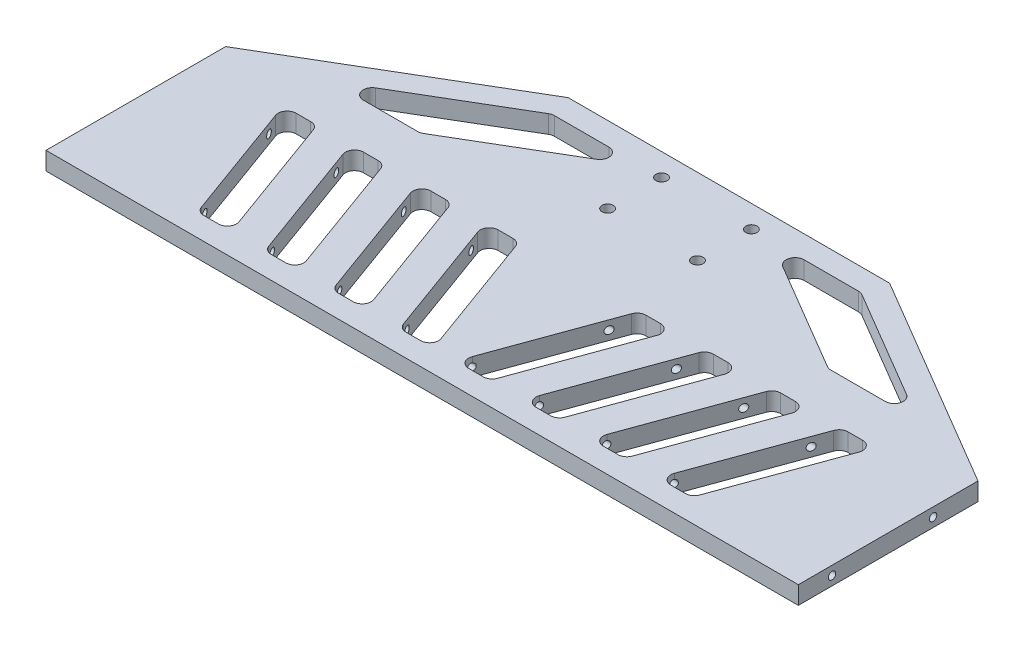
SolidWorks part; units mm, degrees
ref_plane "Ebene vorne" through (0, 0, 0) normal (0, 0, 1) x (1, 0, 0)
ref_plane "Ebene oben" through (0, 0, 0) normal (0, 1, 0) x (1, 0, 0)
ref_plane "Ebene rechts" through (0, 0, 0) normal (1, 0, 0) x (0, 0, -1)
sketch "Skizze3" plane through (0, 0, 0) normal (0, 1, 0) x (1, 0, 0)
  line L0 (0, 0) -> (0, 96.5783) construction
  line L1 (167.5, -40) -> (-167.5, -40)
  line L2 (167.5, -40) -> (167.5, 40)
  line L3 (-167.5, 40) -> (-71.5557, 96.5783)
  line L4 (-167.5, -40) -> (-167.5, 40)
  line L5 (167.5, -40) -> (-167.5, 40) construction
  line L6 (167.5, 40) -> (-167.5, -40) construction
  line L7 (-71.5557, 96.5783) -> (71.5557, 96.5783)
  line L8 (167.5, 40) -> (71.5557, 96.5783)
  circle A0 centre (-20, 86.5783) radius 2.5
  circle A1 centre (-20, 62.5783) radius 2.5
  circle A2 centre (20, 62.5783) radius 2.5
  circle A3 centre (20, 86.5783) radius 2.5
  point P0 (0, 0)
  dimension "D3" = 5
  dimension "D4" = 5
  dimension "D8" = 10
  dimension "D1" = 335
  dimension "D2" = 80
  dimension "D5" = 24
  dimension "D6" = 20
  dimension "D7" = 20
extrude "Aufsatz-Linear austragen2" add sketch "Skizze3" along normal blind 8
hole_wizard "M4 Gewindebohrung1" positions "Skizze4" profile "Skizze6" tap size "M4" standard "DIN" end condition through all
sketch "Skizze4" plane through (167.5, 0, 0) normal (1, 0, 0) x (0, 0, -1)
  line L0 (-40, 4) -> (40, 4) construction
  line L1 (-40, 8) -> (-40, 0) construction
  line L2 (40, 8) -> (40, 0) construction
  point P0 (-25, 4)
  point P2 (20, 4)
  point P12 (-27.9365, 4)
  point P13 (16.7324, 4)
  dimension "D1" = 45
  dimension "D2" = 15
cosmetic thread "Bohrungsgewinde1" parameters "D2"=4
cosmetic thread "Bohrungsgewinde2" parameters "D2"=4
sketch "Skizze6" plane through (167.5, 4, 25) normal (0, 1, 0) x (0, 0, -1)
  line L0 (0, 0) -> (0, 335)
  line L1 (0, 335) -> (1.65, 335)
  line L2 (1.65, 335) -> (1.65, 0)
  line L5 (1.65, 0) -> (0, 0)
  line L11 (0, -6.35) -> (0, 107.95) construction
  dimension "Bohrerdurchmesser" = 3.3
  dimension "Bohrungstiefe" = 335
sketch "Skizze7" plane through (0, 8, 0) normal (0, 1, 0) x (1, 0, 0)
  line L0 (0, 96.5783) -> (0, -40) construction
  line L1 (71.5557, 96.5783) -> (-71.5557, 96.5783) construction
  line L2 (-167.5, -40) -> (167.5, -40) construction
  line L3 (-167.5, 40) -> (167.5, 40) construction
  line L4 (-36.1256, 30) -> (-29.639, 30)
  line L5 (-39.8844, 24.6319) -> (-20.9579, -27.3681)
  line L6 (-25.8803, 27.3681) -> (-6.9538, -24.6319)
  line L7 (-17.1992, -30) -> (-10.7126, -30)
  line L8 (-55.8803, 27.3681) -> (-36.9538, -24.6319)
  line L9 (-47.1992, -30) -> (-40.7126, -30)
  line L10 (-69.8844, 24.6319) -> (-50.9579, -27.3681)
  line L11 (-66.1256, 30) -> (-59.639, 30)
  line L12 (-85.8803, 27.3681) -> (-66.9538, -24.6319)
  line L13 (-77.1992, -30) -> (-70.7126, -30)
  line L14 (-99.8844, 24.6319) -> (-80.9579, -27.3681)
  line L15 (-96.1256, 30) -> (-89.639, 30)
  line L16 (-115.8803, 27.3681) -> (-96.9538, -24.6319)
  line L17 (-107.1992, -30) -> (-100.7126, -30)
  line L18 (-129.8844, 24.6319) -> (-110.9579, -27.3681)
  line L19 (-126.1256, 30) -> (-119.639, 30)
  line L20 (126.1256, 30) -> (119.639, 30)
  line L21 (129.8844, 24.6319) -> (110.9579, -27.3681)
  line L22 (107.1992, -30) -> (100.7126, -30)
  line L23 (115.8803, 27.3681) -> (96.9538, -24.6319)
  line L24 (96.1256, 30) -> (89.639, 30)
  line L25 (99.8844, 24.6319) -> (80.9579, -27.3681)
  line L26 (77.1992, -30) -> (70.7126, -30)
  line L27 (85.8803, 27.3681) -> (66.9538, -24.6319)
  line L28 (66.1256, 30) -> (59.639, 30)
  line L29 (69.8844, 24.6319) -> (50.9579, -27.3681)
  line L30 (47.1992, -30) -> (40.7126, -30)
  line L31 (55.8803, 27.3681) -> (36.9538, -24.6319)
  line L32 (17.1992, -30) -> (10.7126, -30)
  line L33 (25.8803, 27.3681) -> (6.9538, -24.6319)
  line L34 (39.8844, 24.6319) -> (20.9579, -27.3681)
  line L35 (36.1256, 30) -> (29.639, 30)
  arc A0 (-6.9538, -24.6319) -> (-10.7126, -30) centre (-10.7126, -26) cw
  arc A1 (-20.9579, -27.3681) -> (-17.1992, -30) centre (-17.1992, -26) ccw
  arc A2 (-29.639, 30) -> (-25.8803, 27.3681) centre (-29.639, 26) cw
  arc A3 (-39.8844, 24.6319) -> (-36.1256, 30) centre (-36.1256, 26) cw
  arc A4 (-77.1992, -30) -> (-80.9579, -27.3681) centre (-77.1992, -26) cw
  arc A5 (-107.1992, -30) -> (-110.9579, -27.3681) centre (-107.1992, -26) cw
  arc A6 (-96.9538, -24.6319) -> (-100.7126, -30) centre (-100.7126, -26) cw
  arc A7 (-66.9538, -24.6319) -> (-70.7126, -30) centre (-70.7126, -26) cw
  arc A8 (-36.9538, -24.6319) -> (-40.7126, -30) centre (-40.7126, -26) cw
  arc A9 (-55.8803, 27.3681) -> (-59.639, 30) centre (-59.639, 26) ccw
  arc A10 (-69.8844, 24.6319) -> (-66.1256, 30) centre (-66.1256, 26) cw
  arc A11 (-85.8803, 27.3681) -> (-89.639, 30) centre (-89.639, 26) ccw
  arc A12 (-99.8844, 24.6319) -> (-96.1256, 30) centre (-96.1256, 26) cw
  arc A13 (-115.8803, 27.3681) -> (-119.639, 30) centre (-119.639, 26) ccw
  arc A14 (-129.8844, 24.6319) -> (-126.1256, 30) centre (-126.1256, 26) cw
  arc A15 (-47.1992, -30) -> (-50.9579, -27.3681) centre (-47.1992, -26) cw
  arc A16 (47.1992, -30) -> (50.9579, -27.3681) centre (47.1992, -26) ccw
  arc A17 (129.8844, 24.6319) -> (126.1256, 30) centre (126.1256, 26) ccw
  arc A18 (115.8803, 27.3681) -> (119.639, 30) centre (119.639, 26) cw
  arc A19 (99.8844, 24.6319) -> (96.1256, 30) centre (96.1256, 26) ccw
  arc A20 (85.8803, 27.3681) -> (89.639, 30) centre (89.639, 26) cw
  arc A21 (69.8844, 24.6319) -> (66.1256, 30) centre (66.1256, 26) ccw
  arc A22 (55.8803, 27.3681) -> (59.639, 30) centre (59.639, 26) cw
  arc A23 (36.9538, -24.6319) -> (40.7126, -30) centre (40.7126, -26) ccw
  arc A24 (66.9538, -24.6319) -> (70.7126, -30) centre (70.7126, -26) ccw
  arc A25 (96.9538, -24.6319) -> (100.7126, -30) centre (100.7126, -26) ccw
  arc A26 (107.1992, -30) -> (110.9579, -27.3681) centre (107.1992, -26) ccw
  arc A27 (77.1992, -30) -> (80.9579, -27.3681) centre (77.1992, -26) ccw
  arc A28 (39.8844, 24.6319) -> (36.1256, 30) centre (36.1256, 26) ccw
  arc A29 (29.639, 30) -> (25.8803, 27.3681) centre (29.639, 26) ccw
  arc A30 (20.9579, -27.3681) -> (17.1992, -30) centre (17.1992, -26) cw
  arc A31 (6.9538, -24.6319) -> (10.7126, -30) centre (10.7126, -26) ccw
  point P28 (-5, -30)
  point P33 (-26.8382, 30)
  point P36 (-41.8382, 30)
  point P109 (41.8382, 30)
  point P110 (26.8382, 30)
  point P111 (5, -30)
  dimension "D7" = 4
  dimension "D8" = 4
  dimension "D1" = 15
  dimension "D2" = 110
  dimension "D3" = 10
  dimension "D4" = 10
  dimension "D5" = 10
  dimension "D6" = 4
extrude "Schnitt-Linear austragen1" cut sketch "Skizze7" against normal blind 8
sketch "Skizze8" plane through (0, 8, 0) normal (0, 1, 0) x (1, 0, 0)
  line L0 (-118.2295, 57.4455) -> (-69.767, 86.0238)
  line L1 (-116.1977, 50) -> (-91.9471, 50)
  line L2 (-67.7352, 86.5783) -> (-43.4846, 86.5783)
  line L3 (-89.9152, 50.5545) -> (-41.4528, 79.1328)
  line L5 (71.5557, 96.5783) -> (-71.5557, 96.5783) construction
  line L7 (-71.5557, 96.5783) -> (-167.5, 40) construction
  line L8 (0, 96.5783) -> (0, 0) construction
  line L9 (89.9152, 50.5545) -> (41.4528, 79.1328)
  line L10 (67.7352, 86.5783) -> (43.4846, 86.5783)
  line L11 (116.1977, 50) -> (91.9471, 50)
  line L12 (118.2295, 57.4455) -> (69.767, 86.0238)
  arc A0 (-91.9471, 50) -> (-89.9152, 50.5545) centre (-91.9471, 54) ccw
  arc A1 (-43.4846, 86.5783) -> (-41.4528, 79.1328) centre (-43.4846, 82.5783) cw
  arc A2 (-69.767, 86.0238) -> (-67.7352, 86.5783) centre (-67.7352, 82.5783) cw
  arc A3 (-116.1977, 50) -> (-118.2295, 57.4455) centre (-116.1977, 54) cw
  arc A4 (116.1977, 50) -> (118.2295, 57.4455) centre (116.1977, 54) ccw
  arc A5 (69.767, 86.0238) -> (67.7352, 86.5783) centre (67.7352, 82.5783) ccw
  arc A6 (43.4846, 86.5783) -> (41.4528, 79.1328) centre (43.4846, 82.5783) ccw
  arc A7 (91.9471, 50) -> (89.9152, 50.5545) centre (91.9471, 54) cw
  point P11 (-90.8555, 50)
  point P18 (-130.8555, 50)
  point P34 (130.8555, 50)
  point P35 (90.8555, 50)
  dimension "D5" = 4
  dimension "D1" = 10
  dimension "D2" = 10
  dimension "D3" = 10
  dimension "D4" = 40
extrude "Schnitt-Linear austragen2" cut sketch "Skizze8" against normal blind 8
